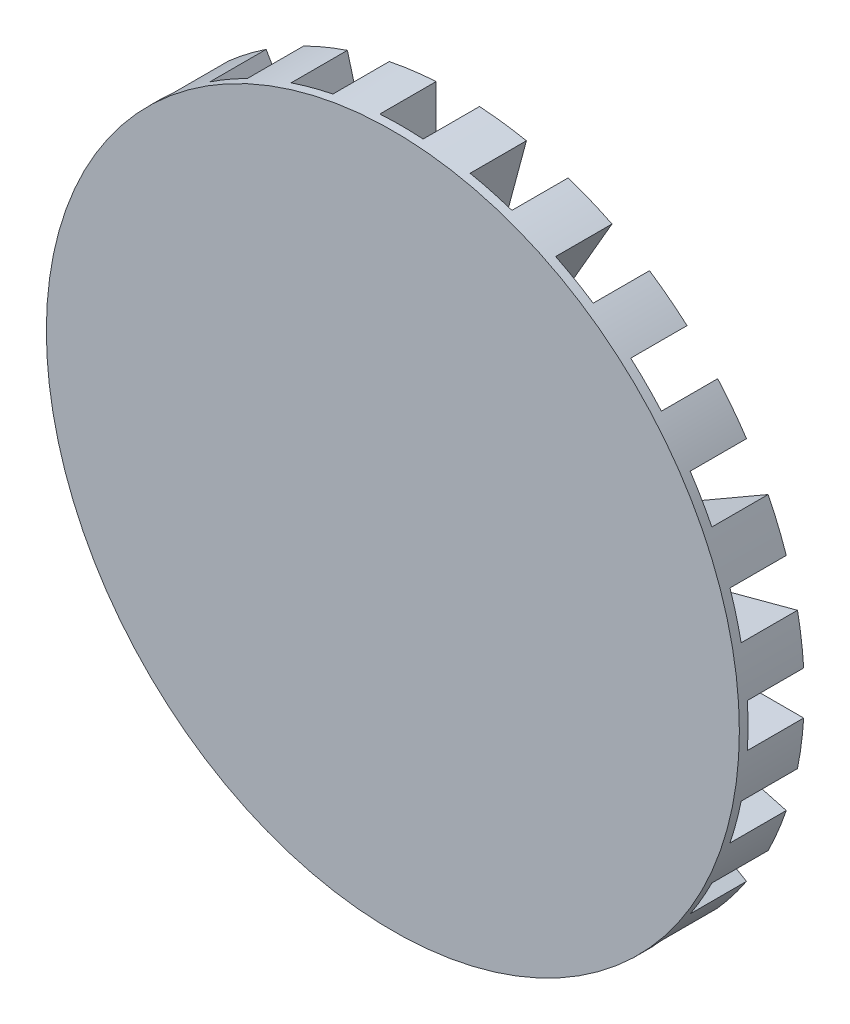
SolidWorks part; units mm, degrees
material "PUR"
ref_plane "Front Plane" through (0, 0, 0) normal (0, 0, 1) x (1, 0, 0)
ref_plane "Top Plane" through (0, 0, 0) normal (0, 1, 0) x (1, 0, 0)
ref_plane "Right Plane" through (0, 0, 0) normal (1, 0, 0) x (0, 0, -1)
sketch "Sketch1" plane through (0, 0, 0) normal (0, 0, 1) x (1, 0, 0)
  circle A0 centre (0, 0) radius 80
  circle A1 centre (0, 0) radius 100 construction
  circle A4 centre (0, 0) radius 100 construction
  dimension "D1" = 20
extrude "Boss-Extrude1" add sketch "Sketch1" along normal blind 2 from offset 13
sketch "Sketch3" plane through (0, 0, 15) normal (0, 0, 1) x (1, 0, 0)
  line L0 (0, 0) -> (0, -80) construction
  line L1 (0, 0) -> (-20.7055, -77.2741) construction
  line L2 (-5, -79.8436) -> (-5, -37.9788)
  line L3 (-5, -37.9788) -> (-15.8354, -78.4171)
  line L4 (-5, -58.9112) -> (0, -58.9112) construction
  line L5 (-10.4177, -58.1979) -> (-15.2473, -56.9038) construction
  circle A0 centre (0, 0) radius 80 construction
  arc A1 (-5, -79.8436) -> (-15.8354, -78.4171) centre (0, 0) cw
  dimension "D1" = 10
  dimension "D2" = 15
extrude "Boss-Extrude2" add sketch "Sketch3" against normal up to surface (15 mm away)
fillet "Fillet1" radius 0.5 1 edges at (-5, -37.9788, 6.5)
pattern_circular "CirPattern1" count 24 over 360 about axis through (0, 0, 15) along (0, 0, -1) of "Boss-Extrude2", "Fillet1"
sketch "Sketch4" plane through (0, 0, 0) normal (0, 0, -1) x (-1, 0, 0)
  line L0 (-10.4421, 79.3156) -> (0, 0) construction
  line L1 (0, 0) -> (0, 80) construction
  circle A0 centre (-9.7895, 74.3584) radius 1
  arc A1 (-5, 79.8436) -> (-15.8354, 78.4171) centre (0, 0) ccw construction
  arc A2 (5, 79.8436) -> (-5, 79.8436) centre (0, 0) ccw construction
  dimension "D2" = 2
  dimension "D1" = 75
extrude "Cut-Extrude1" cut sketch "Sketch4" against normal blind 8
pattern_circular "CirPattern2" count 12 over 360 about axis through (0, 0, 15) along (0, 0, 1) of "Cut-Extrude1"
